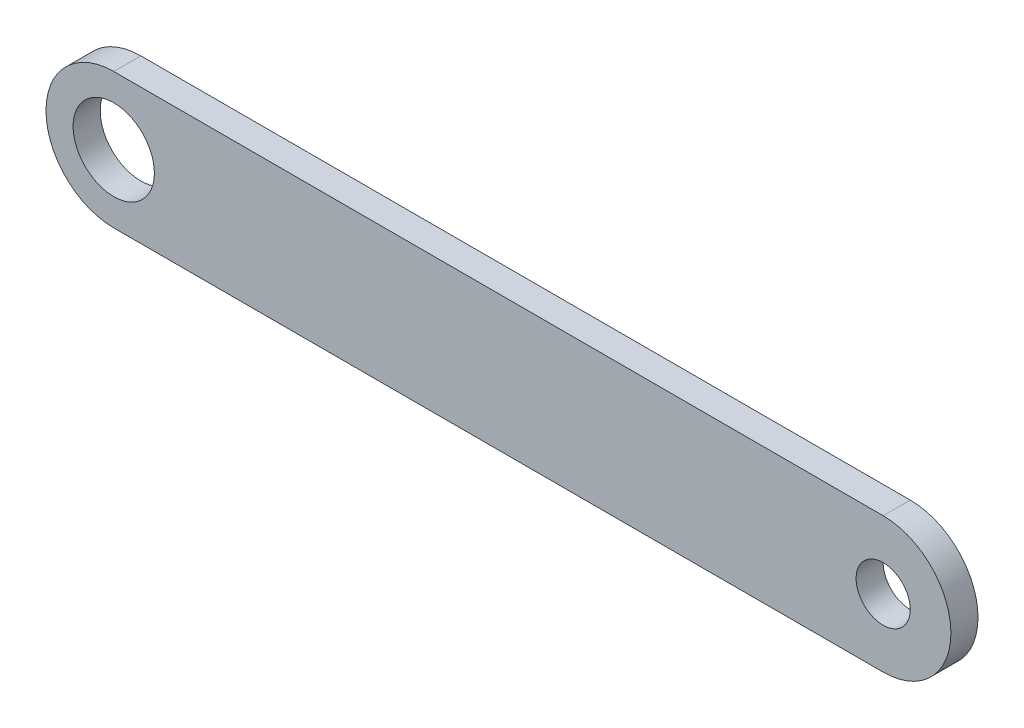
SolidWorks part; units mm, degrees
ref_plane "Front Plane" through (0, 0, 0) normal (0, 0, 1) x (1, 0, 0)
ref_plane "Top Plane" through (0, 0, 0) normal (0, 1, 0) x (1, 0, 0)
ref_plane "Right Plane" through (0, 0, 0) normal (1, 0, 0) x (0, 0, -1)
sketch "Sketch1" plane through (0, 0, 0) normal (0, 0, 1) x (1, 0, 0)
  line L0 (-71, 0) -> (71, 0) construction
  line L1 (-71, 12.5) -> (71, 12.5)
  line L2 (-71, -12.5) -> (71, -12.5)
  arc A0 (-71, 12.5) -> (-71, -12.5) centre (-71, 0) ccw
  arc A1 (71, -12.5) -> (71, 12.5) centre (71, 0) ccw
  point P2 (0, 0)
  dimension "D1" = 142
  dimension "D3" = 25
extrude "Boss-Extrude1" add sketch "Sketch1" along normal blind 5
hole_wizard "M14 Clearance Hole1" positions "Sketch4" profile "Sketch5" hole size "M14" standard "ANSI Metric" end condition through all
sketch "Sketch4" plane through (0, 0, 5) normal (0, 0, 1) x (1, 0, 0)
  point P0 (-71, 0)
sketch "Sketch5" plane through (-71, 0, 5) normal (1, 0, 0) x (0, -1, 0)
  line L0 (0, 0) -> (0, 5)
  line L1 (0, 5) -> (7.5, 5)
  line L2 (7.5, 5) -> (7.5, 0)
  line L5 (7.5, 0) -> (0, 0)
  line L11 (0, -6.35) -> (0, 107.95) construction
  dimension "Thru Hole Dia." = 15
  dimension "Thru Hole Depth" = 5
hole_wizard "M8 Clearance Hole1" positions "Sketch6" profile "Sketch7" hole size "M8" standard "ANSI Metric" end condition through all
sketch "Sketch6" plane through (0, 0, 5) normal (0, 0, 1) x (1, 0, 0)
  point P0 (71, 0)
sketch "Sketch7" plane through (71, 0, 5) normal (1, 0, 0) x (0, -1, 0)
  line L0 (0, 0) -> (0, 5)
  line L1 (0, 5) -> (5, 5)
  line L2 (5, 5) -> (5, 0)
  line L5 (5, 0) -> (0, 0)
  line L11 (0, -6.35) -> (0, 107.95) construction
  dimension "Thru Hole Dia." = 10
  dimension "Thru Hole Depth" = 5
